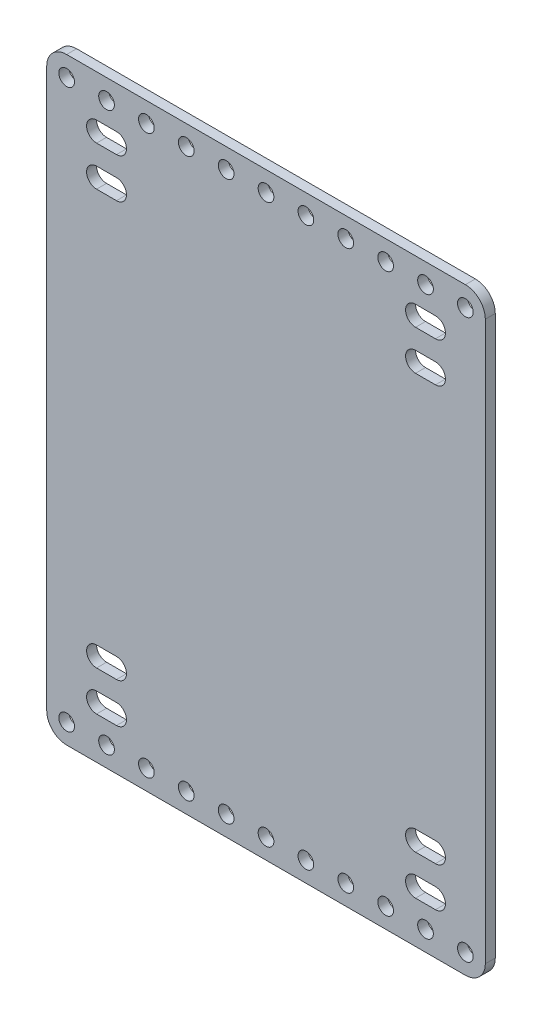
SolidWorks part; units mm, degrees
ref_plane "Front Plane" through (0, 0, 0) normal (0, 0, 1) x (1, 0, 0)
ref_plane "Top Plane" through (0, 0, 0) normal (0, 1, 0) x (1, 0, 0)
ref_plane "Right Plane" through (0, 0, 0) normal (1, 0, 0) x (0, 0, -1)
sketch "Sketch1" plane through (0, 0, 0) normal (0, 0, 1) x (1, 0, 0)
  line L1 (-367.5063, 254) -> (-240.5063, 254)
  line L2 (-373.8563, 247.65) -> (-373.8563, 69.85)
  line L3 (-367.5063, 63.5) -> (-240.5063, 63.5)
  line L4 (-234.1563, 247.65) -> (-234.1563, 69.85)
  arc A0 (-373.8563, 69.85) -> (-367.5063, 63.5) centre (-367.5063, 69.85) ccw
  arc A1 (-240.5063, 63.5) -> (-234.1563, 69.85) centre (-240.5063, 69.85) ccw
  arc A2 (-240.5063, 254) -> (-234.1563, 247.65) centre (-240.5063, 247.65) cw
  arc A3 (-367.5063, 254) -> (-373.8563, 247.65) centre (-367.5063, 247.65) ccw
  point P6 (-373.8563, 63.5)
  point P11 (-234.1563, 254)
  point P14 (-373.8563, 254)
  dimension "D3" = 6.35
  dimension "D1" = 139.7
  dimension "D2" = 190.5
extrude "Boss-Extrude1" add sketch "Sketch1" along normal blind 3.175
sketch "Sketch3" plane through (0, 0, 3.175) normal (0, 0, 1) x (1, 0, 0)
  line L0 (-373.8563, 247.65) -> (-373.8563, 69.85) construction
  line L1 (-240.5063, 254) -> (-367.5063, 254) construction
  line L3 (-367.5063, 63.5) -> (-240.5063, 63.5) construction
  circle A1 centre (-367.5063, 247.65) radius 2.5
  circle A28 centre (-367.5062, 69.85) radius 2.5
  circle A30 centre (-354.8063, 247.65) radius 2.5
  circle A31 centre (-354.8063, 69.85) radius 2.5
  circle A32 centre (-342.1063, 247.65) radius 2.5
  circle A33 centre (-342.1063, 69.85) radius 2.5
  circle A34 centre (-329.4063, 247.65) radius 2.5
  circle A35 centre (-329.4063, 69.85) radius 2.5
  circle A36 centre (-316.7063, 247.65) radius 2.5
  circle A37 centre (-316.7063, 69.85) radius 2.5
  circle A38 centre (-304.0063, 247.65) radius 2.5
  circle A39 centre (-304.0063, 69.85) radius 2.5
  circle A40 centre (-291.3063, 247.65) radius 2.5
  circle A41 centre (-291.3063, 69.85) radius 2.5
  circle A42 centre (-278.6063, 247.65) radius 2.5
  circle A43 centre (-278.6063, 69.85) radius 2.5
  circle A44 centre (-265.9063, 247.65) radius 2.5
  circle A45 centre (-265.9063, 69.85) radius 2.5
  circle A46 centre (-253.2063, 247.65) radius 2.5
  circle A47 centre (-253.2063, 69.85) radius 2.5
  circle A48 centre (-240.5063, 247.65) radius 2.5
  circle A49 centre (-240.5063, 69.85) radius 2.5
  circle A50 centre (-367.5062, 209.55) radius 2.5 [skipped]
  circle A51 centre (-367.5062, 196.85) radius 2.5 [skipped]
  circle A52 centre (-367.5062, 184.15) radius 2.5 [skipped]
  circle A53 centre (-367.5062, 171.45) radius 2.5 [skipped]
  circle A54 centre (-367.5062, 158.75) radius 2.5 [skipped]
  circle A55 centre (-367.5062, 146.05) radius 2.5 [skipped]
  circle A56 centre (-367.5062, 133.35) radius 2.5 [skipped]
  circle A57 centre (-367.5062, 120.65) radius 2.5 [skipped]
  circle A58 centre (-367.5062, 107.95) radius 2.5 [skipped]
  circle A59 centre (-367.5062, 95.25) radius 2.5 [skipped]
  circle A60 centre (-367.5062, 82.55) radius 2.5 [skipped]
  circle A61 centre (-367.5062, 234.95) radius 2.5 [skipped]
  circle A62 centre (-367.5062, 222.25) radius 2.5 [skipped]
  point P12 (-348.4563, 247.65)
  point P13 (-348.4563, 76.2)
  dimension "D1" = 5
  dimension "D8" = 5
  dimension "D10" = 5
  dimension "D2" = 6.35
  dimension "D3" = 6.35
  dimension "D9" = 19.05
  dimension "D11" = 6.35
  dimension "D12" = 19.05
  dimension "D13" = 6.35
  dimension "D7" = 15
  dimension "D14" = 10
extrude "Cut-Extrude2" cut sketch "Sketch3" against normal through all contours A1 | A31 | A33 | A28 | A35 | A37 | A39 | A41 | A43 | A45 | A46 | A44 | A30 | A32 | A34 | A36 | A40 | A48 | A28 | A47 | A42 | A38 | A49 region at (-367.5063, 247.65, 3.175) region at (-367.5062, 69.85, 3.175) region at (-354.8063, 247.65, 3.175) region at (-354.8063, 69.85, 3.175) region at (-342.1063, 247.65, 3.175) region at (-342.1063, 69.85, 3.175) region at (-329.4063, 247.65, 3.175) region at (-329.4063, 69.85, 3.175) region at (-316.7063, 247.65, 3.175) region at (-316.7063, 69.85, 3.175) region at (-304.0063, 69.85, 3.175) region at (-291.3063, 247.65, 3.175) region at (-291.3063, 69.85, 3.175) region at (-278.6063, 69.85, 3.175) region at (-265.9063, 247.65, 3.175) region at (-265.9063, 69.85, 3.175) region at (-253.2063, 247.65, 3.175) region at (-240.5063, 247.65, 3.175)
sketch "Sketch4" plane through (0, 0, 3.175) normal (0, 0, 1) x (1, 0, 0)
  line L0 (-357.9813, 237.49) -> (-351.6313, 237.49) construction
  line L1 (-357.9813, 240.665) -> (-351.6313, 240.665)
  line L2 (-357.9813, 234.315) -> (-351.6313, 234.315)
  line L3 (-357.9813, 224.79) -> (-351.6313, 224.79) construction
  line L4 (-357.9813, 227.965) -> (-351.6313, 227.965)
  line L5 (-357.9813, 221.615) -> (-351.6313, 221.615)
  line L6 (-373.8563, 247.65) -> (-373.8563, 69.85) construction
  line L7 (-240.5063, 254) -> (-367.5063, 254) construction
  line L8 (-304.0063, 254) -> (-304.0063, 63.5) construction
  line L9 (-367.5063, 63.5) -> (-240.5063, 63.5) construction
  line L10 (-373.8563, 158.75) -> (-234.1563, 158.75) construction
  line L11 (-234.1563, 69.85) -> (-234.1563, 247.65) construction
  line L12 (-250.0313, 237.49) -> (-256.3813, 237.49) construction
  line L13 (-250.0313, 240.665) -> (-256.3813, 240.665)
  line L14 (-250.0313, 234.315) -> (-256.3813, 234.315)
  line L15 (-250.0313, 224.79) -> (-256.3813, 224.79) construction
  line L16 (-250.0313, 227.965) -> (-256.3813, 227.965)
  line L17 (-250.0313, 221.615) -> (-256.3813, 221.615)
  line L18 (-357.9813, 237.49) -> (-351.6313, 237.49) construction
  line L19 (-357.9813, 240.665) -> (-351.6313, 240.665)
  line L20 (-357.9813, 234.315) -> (-351.6313, 234.315)
  line L21 (-357.9813, 224.79) -> (-351.6313, 224.79) construction
  line L22 (-357.9813, 227.965) -> (-351.6313, 227.965)
  line L23 (-357.9813, 221.615) -> (-351.6313, 221.615)
  line L24 (-250.0313, 224.79) -> (-256.3813, 224.79) construction
  line L25 (-250.0313, 227.965) -> (-256.3813, 227.965)
  line L26 (-250.0313, 221.615) -> (-256.3813, 221.615)
  line L27 (-250.0313, 237.49) -> (-256.3813, 237.49) construction
  line L28 (-250.0313, 240.665) -> (-256.3813, 240.665)
  line L29 (-250.0313, 234.315) -> (-256.3813, 234.315)
  line L30 (-250.0313, 92.71) -> (-256.3813, 92.71) construction
  line L31 (-250.0313, 89.535) -> (-256.3813, 89.535)
  line L32 (-250.0313, 95.885) -> (-256.3813, 95.885)
  line L33 (-250.0313, 80.01) -> (-256.3813, 80.01) construction
  line L34 (-250.0313, 76.835) -> (-256.3813, 76.835)
  line L35 (-250.0313, 83.185) -> (-256.3813, 83.185)
  line L36 (-357.9813, 92.71) -> (-351.6313, 92.71) construction
  line L37 (-357.9813, 89.535) -> (-351.6313, 89.535)
  line L38 (-357.9813, 95.885) -> (-351.6313, 95.885)
  line L39 (-357.9813, 80.01) -> (-351.6313, 80.01) construction
  line L40 (-357.9813, 76.835) -> (-351.6313, 76.835)
  line L41 (-357.9813, 83.185) -> (-351.6313, 83.185)
  arc A0 (-357.9813, 240.665) -> (-357.9813, 234.315) centre (-357.9813, 237.49) ccw
  arc A1 (-351.6313, 234.315) -> (-351.6313, 240.665) centre (-351.6313, 237.49) ccw
  arc A2 (-357.9813, 227.965) -> (-357.9813, 221.615) centre (-357.9813, 224.79) ccw
  arc A3 (-351.6313, 221.615) -> (-351.6313, 227.965) centre (-351.6313, 224.79) ccw
  arc A4 (-250.0313, 240.665) -> (-250.0313, 234.315) centre (-250.0313, 237.49) cw
  arc A5 (-256.3813, 234.315) -> (-256.3813, 240.665) centre (-256.3813, 237.49) cw
  arc A6 (-250.0313, 227.965) -> (-250.0313, 221.615) centre (-250.0313, 224.79) cw
  arc A7 (-256.3813, 221.615) -> (-256.3813, 227.965) centre (-256.3813, 224.79) cw
  arc A8 (-357.9813, 240.665) -> (-357.9813, 234.315) centre (-357.9813, 237.49) ccw
  arc A9 (-351.6313, 234.315) -> (-351.6313, 240.665) centre (-351.6313, 237.49) ccw
  arc A10 (-357.9813, 227.965) -> (-357.9813, 221.615) centre (-357.9813, 224.79) ccw
  arc A11 (-351.6313, 221.615) -> (-351.6313, 227.965) centre (-351.6313, 224.79) ccw
  arc A12 (-250.0313, 227.965) -> (-250.0313, 221.615) centre (-250.0313, 224.79) cw
  arc A13 (-256.3813, 221.615) -> (-256.3813, 227.965) centre (-256.3813, 224.79) cw
  arc A14 (-250.0313, 240.665) -> (-250.0313, 234.315) centre (-250.0313, 237.49) cw
  arc A15 (-256.3813, 234.315) -> (-256.3813, 240.665) centre (-256.3813, 237.49) cw
  arc A16 (-250.0313, 89.535) -> (-250.0313, 95.885) centre (-250.0313, 92.71) ccw
  arc A17 (-256.3813, 95.885) -> (-256.3813, 89.535) centre (-256.3813, 92.71) ccw
  arc A18 (-250.0313, 76.835) -> (-250.0313, 83.185) centre (-250.0313, 80.01) ccw
  arc A19 (-256.3813, 83.185) -> (-256.3813, 76.835) centre (-256.3813, 80.01) ccw
  arc A20 (-357.9813, 89.535) -> (-357.9813, 95.885) centre (-357.9813, 92.71) cw
  arc A21 (-351.6313, 95.885) -> (-351.6313, 89.535) centre (-351.6313, 92.71) cw
  arc A22 (-357.9813, 76.835) -> (-357.9813, 83.185) centre (-357.9813, 80.01) cw
  arc A23 (-351.6313, 83.185) -> (-351.6313, 76.835) centre (-351.6313, 80.01) cw
  point P2 (-354.8063, 237.49)
  point P7 (-354.8063, 224.79)
  point P28 (-253.2063, 237.49)
  point P35 (-253.2063, 224.79)
  point P42 (-354.8063, 237.49)
  point P49 (-354.8063, 224.79)
  point P56 (-253.2063, 224.79)
  point P63 (-253.2063, 237.49)
  point P70 (-253.2063, 92.71)
  point P77 (-253.2063, 80.01)
  point P84 (-354.8063, 92.71)
  point P91 (-354.8063, 80.01)
  dimension "D3" = 3.175
  dimension "D1" = 15.875
  dimension "D2" = 16.51
  dimension "D4" = 15.875
  dimension "D5" = 6.35
  dimension "D6" = 12.7
extrude "Cut-Extrude3" cut sketch "Sketch4" against normal through all contours L2 A1 L1 A0 | L5 A3 L4 A2 | A7 L17 A6 L16 | A5 L14 A4 L13 | A21 L38 A20 L37 | A23 L41 A22 L40 | L32 A17 L31 A16 | L35 A19 L34 A18 region at (-354.8063, 237.49, 3.175) region at (-354.8063, 224.79, 3.175) region at (-253.2063, 237.49, 3.175) region at (-253.2063, 224.79, 3.175) region at (-253.2063, 92.71, 3.175) region at (-253.2063, 80.01, 3.175) region at (-354.8063, 92.71, 3.175) region at (-354.8063, 80.01, 3.175)
